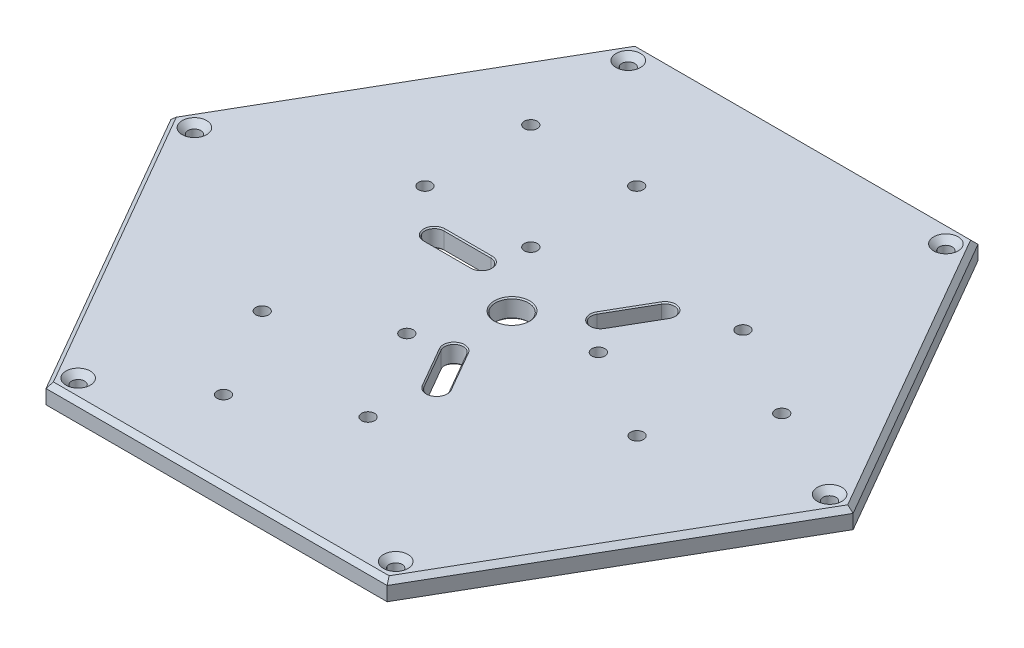
SolidWorks part; units mm, degrees
material "5052-H32"
ref_plane "Front Plane" through (0, 0, 0) normal (0, 0, 1) x (1, 0, 0)
ref_plane "Top Plane" through (0, 0, 0) normal (0, 1, 0) x (1, 0, 0)
ref_plane "Right Plane" through (0, 0, 0) normal (1, 0, 0) x (0, 0, -1)
sketch "Sketch1" plane through (0, 0, 0) normal (0, 1, 0) x (1, 0, 0)
  line L1 (72.5, 125.5737) -> (-72.5, 125.5737)
  line L2 (-72.5, 125.5737) -> (-145, 0)
  line L3 (-145, 0) -> (-72.5, -125.5737)
  line L4 (-72.5, -125.5737) -> (72.5, -125.5737)
  line L5 (72.5, -125.5737) -> (145, 0)
  line L6 (145, 0) -> (72.5, 125.5737)
  circle A0 centre (0, 0) radius 125.5737 construction
  dimension "D1" = 145
extrude "Boss-Extrude1" add sketch "Sketch1" along normal blind 8
sketch "Sketch2" plane through (0, 0, 0) normal (0, 1, 0) x (1, 0, 0)
  line L0 (0, 0) -> (108.75, 62.7868) construction
  line L1 (145, 0) -> (72.5, 125.5737) construction
  line L2 (75.5513, 30.8586) -> (53.0513, -8.1125) construction
  line L3 (66.5368, -29.7548) -> (27.5657, -7.2548) construction
  line L6 (33.5657, 3.1375) -> (72.5368, -19.3625) construction
  line L7 (72.5368, -19.3625) -> (95.0368, 19.6086) construction
  line L8 (95.0368, 19.6086) -> (56.0657, 42.1086) construction
  line L9 (56.0657, 42.1086) -> (33.5657, 3.1375) construction
  line L10 (-14.0657, -30.6375) -> (-53.0368, -53.1375) construction
  line L11 (8.4343, -69.6086) -> (-14.0657, -30.6375) construction
  line L12 (-30.5368, -92.1086) -> (8.4343, -69.6086) construction
  line L13 (-53.0368, -53.1375) -> (-30.5368, -92.1086) construction
  line L14 (-19.5, 27.5) -> (-19.5, 72.5) construction
  line L15 (-64.5, 27.5) -> (-19.5, 27.5) construction
  line L16 (-64.5, 72.5) -> (-64.5, 27.5) construction
  line L17 (-19.5, 72.5) -> (-64.5, 72.5) construction
  line L19 (53.0513, -8.1125) -> (43.3013, -25) construction
  line L21 (108.75, -62.7868) -> (0, 0) construction
  line L22 (72.5, -125.5737) -> (145, 0) construction
  point P9 (47.0513, -18.5048)
  point P18 (33.5657, 3.1375)
  point P19 (56.0657, 42.1086)
  point P20 (95.0368, 19.6086)
  point P21 (72.5368, -19.3625)
  point P31 (0, 0)
  dimension "D1" = 45
  dimension "D2" = 45
  dimension "D4" = 7.5
  dimension "D5" = 12
  dimension "D6" = 50
  dimension "D3" = 3
sketch "Sketch5" plane through (0, 8, 0) normal (0, 1, 0) x (1, 0, 0)
  circle A0 centre (0, 0) radius 7
  dimension "D1" = 14
extrude "Cut-Extrude1" cut sketch "Sketch5" against normal through all
hole_wizard "CSK for M5 Flat Head Machine Screw1" positions "Sketch7" profile "Sketch6" countersink size "M5" standard "ANSI Metric" end condition through all
sketch "Sketch7" plane through (0, 0, 0) normal (0, -1, 0) x (-1, 0, 0)
  point P0 (64.5, 27.5)
  point P3 (19.5, 27.5)
  point P6 (19.5, 72.5)
  point P9 (64.5, 72.5)
  point P12 (-33.5657, 3.1375)
  point P15 (-72.5368, -19.3625)
  point P18 (-95.0368, 19.6086)
  point P21 (-56.0657, 42.1086)
  point P24 (14.0657, -30.6375)
  point P27 (-8.4343, -69.6086)
  point P30 (30.5368, -92.1086)
  point P33 (53.0368, -53.1375)
sketch "Sketch6" plane through (-64.5, 0, -27.5) normal (1, 0, 0) x (0, 0, -1)
  line L0 (0, 0) -> (0, 8)
  line L1 (0, 8) -> (2.75, 8)
  line L2 (2.75, 8) -> (2.75, 2.45)
  line L3 (2.75, 2.45) -> (5.2, 0)
  line L5 (5.2, 0) -> (0, 0)
  line L6 (-2.75, 2.45) -> (-5.2, 0) construction
  line L11 (0, -6.35) -> (0, 107.95) construction
  dimension "Thru Hole Dia." = 5.5
  dimension "Thru Hole Depth" = 8
  dimension "Near C'Sink Dia." = 10.4
  dimension "Near C'Sink Angle" = 90
sketch "Sketch9" plane through (0, 0, 0) normal (0, -1, 0) x (1, 0, 0)
  line L0 (32.2093, -32.7881) -> (22.2093, -15.4676) construction
  line L1 (28.7452, -34.7881) -> (18.7452, -17.4676)
  line L2 (35.6734, -30.7881) -> (25.6734, -13.4676)
  line L3 (19.7093, -11.1375) -> (42.2093, -50.1086) construction
  line L4 (95.0368, -19.6086) -> (56.0657, -42.1086) construction
  line L5 (33.5657, -3.1375) -> (72.5368, 19.3625) construction
  line L6 (56.0657, -42.1086) -> (33.5657, -3.1375) construction
  line L7 (-44.5, -11.5) -> (-24.5, -11.5) construction
  line L8 (-44.5, -7.5) -> (-24.5, -7.5)
  line L9 (-44.5, -15.5) -> (-24.5, -15.5)
  line L10 (12.2907, 44.2881) -> (2.2907, 26.9676) construction
  line L11 (15.7548, 42.2881) -> (5.7548, 24.9676)
  line L12 (8.8266, 46.2881) -> (-1.1734, 28.9676)
  arc A0 (28.7452, -34.7881) -> (35.6734, -30.7881) centre (32.2093, -32.7881) ccw
  arc A1 (25.6734, -13.4676) -> (18.7452, -17.4676) centre (22.2093, -15.4676) ccw
  arc A2 (-44.5, -7.5) -> (-44.5, -15.5) centre (-44.5, -11.5) ccw
  arc A3 (-24.5, -15.5) -> (-24.5, -7.5) centre (-24.5, -11.5) ccw
  arc A4 (15.7548, 42.2881) -> (8.8266, 46.2881) centre (12.2907, 44.2881) ccw
  arc A5 (-1.1734, 28.9676) -> (5.7548, 24.9676) centre (2.2907, 26.9676) ccw
  point P2 (27.2093, -24.1279)
  point P19 (-34.5, -11.5)
  point P26 (7.2907, 35.6279)
  point P31 (0, 0)
  dimension "D1" = 16
  dimension "D2" = 8
  dimension "D3" = 20
  dimension "D5" = 30
  dimension "D4" = 3
extrude "Cut-Extrude3" cut sketch "Sketch9" against normal through all
sketch "Sketch10" plane through (0, 8, 0) normal (0, 1, 0) x (1, 0, 0)
  line L0 (145, 0) -> (0, 0) construction
  point P4 (135, 0)
  point P7 (67.5, -116.9134)
  point P8 (-67.5, -116.9134)
  point P9 (-135, 0)
  point P10 (-67.5, 116.9134)
  point P11 (67.5, 116.9134)
  point P12 (0, 0)
  dimension "D2" = 10
  dimension "D1" = 6
hole_wizard "CSK for M5 Flat Head Machine Screw2" positions "Sketch14" profile "Sketch13" countersink size "M5" standard "ANSI Metric"
sketch "Sketch14" plane through (0, 8, 0) normal (0, 1, 0) x (1, 0, 0)
  point P0 (-135, 0)
  point P3 (-67.5, -116.9134)
  point P6 (67.5, -116.9134)
  point P9 (135, 0)
  point P12 (67.5, 116.9134)
  point P15 (-67.5, 116.9134)
sketch "Sketch13" plane through (-135, 8, 0) normal (1, 0, 0) x (0, 0, 1)
  line L0 (0, 0) -> (0, 11.6524)
  line L1 (0, 11.6524) -> (2.75, 10)
  line L2 (2.75, 10) -> (2.75, 2.45)
  line L3 (2.75, 2.45) -> (5.2, 0)
  line L5 (5.2, 0) -> (0, 0)
  line L6 (-2.75, 2.45) -> (-5.2, 0) construction
  line L10 (0, 11.6524) -> (-2.75, 10) construction
  line L11 (0, -6.35) -> (0, 107.95) construction
  dimension "Hole Dia." = 5.5
  dimension "Hole Depth" = 10
  dimension "Near C'Sink Dia." = 10.4
  dimension "Near C'Sink Angle" = 90
  dimension "Drill Angle" = 118
chamfer "Chamfer1" distance 0.5 angle 45 24 edges at (-34.5, 0, -15.5) (-20.5, 0, -11.5) (-48.5, 0, -11.5) (-34.5, 0, -7.5) (23.7452, 0, -26.1279) (34.2093, 0, -36.2522) (20.2093, 0, -12.0035) (30.6734, 0, -22.1279) (3.8266, 0, 37.6279) (0.2907, 0, 23.5035) (14.2907, 0, 47.7522) (10.7548, 0, 33.6279) (-34.5, 8, -15.5) (-20.5, 8, -11.5) (-48.5, 8, -11.5) (-34.5, 8, -7.5) (23.7452, 8, -26.1279) (34.2093, 8, -36.2522) (20.2093, 8, -12.0035) (30.6734, 8, -22.1279) (3.8266, 8, 37.6279) (0.2907, 8, 23.5035) (14.2907, 8, 47.7522) (10.7548, 8, 33.6279)
sketch "Sketch8" plane through (0, 0, 0) normal (0, -1, 0) x (1, 0, 0)
  line L0 (104.25, 70.5811) -> (113.25, 54.9926)
  line L1 (104.25, 70.5811) -> (66.9471, 49.0442)
  line L2 (113.25, 54.9926) -> (75.9471, 33.4558)
  line L3 (66.9471, 49.0442) -> (75.9471, 33.4558)
  line L4 (72.5, 125.5737) -> (145, 0) construction
  line L5 (108.75, 62.7868) -> (0, 0) construction
  line L7 (9, -125.5737) -> (-9, -125.5737)
  line L8 (9, -125.5737) -> (9, -82.5)
  line L9 (-9, -125.5737) -> (-9, -82.5)
  line L10 (9, -82.5) -> (-9, -82.5)
  line L11 (-113.25, 54.9926) -> (-104.25, 70.5811)
  line L12 (-113.25, 54.9926) -> (-75.9471, 33.4558)
  line L13 (-104.25, 70.5811) -> (-66.9471, 49.0442)
  line L14 (-75.9471, 33.4558) -> (-66.9471, 49.0442)
  circle A0 centre (0, 0) radius 7 construction
  point P6 (108.75, 62.7868)
  point P22 (0, 0)
  dimension "D1" = 18
  dimension "D2" = 10
  dimension "D3" = 3
extrude "Cut-Extrude2" [suppressed] cut sketch "Sketch8" against normal through all
chamfer "Chamfer3" distance 0.5 angle 45 2 edges at (0, 8, 7) (0, 0, 7)
chamfer "Chamfer4" distance 2 angle 45 6 edges at (0, 8, 125.5737) (108.75, 8, 62.7868) (108.75, 8, -62.7868) (0, 8, -125.5737) (-108.75, 8, -62.7868) (-108.75, 8, 62.7868)
